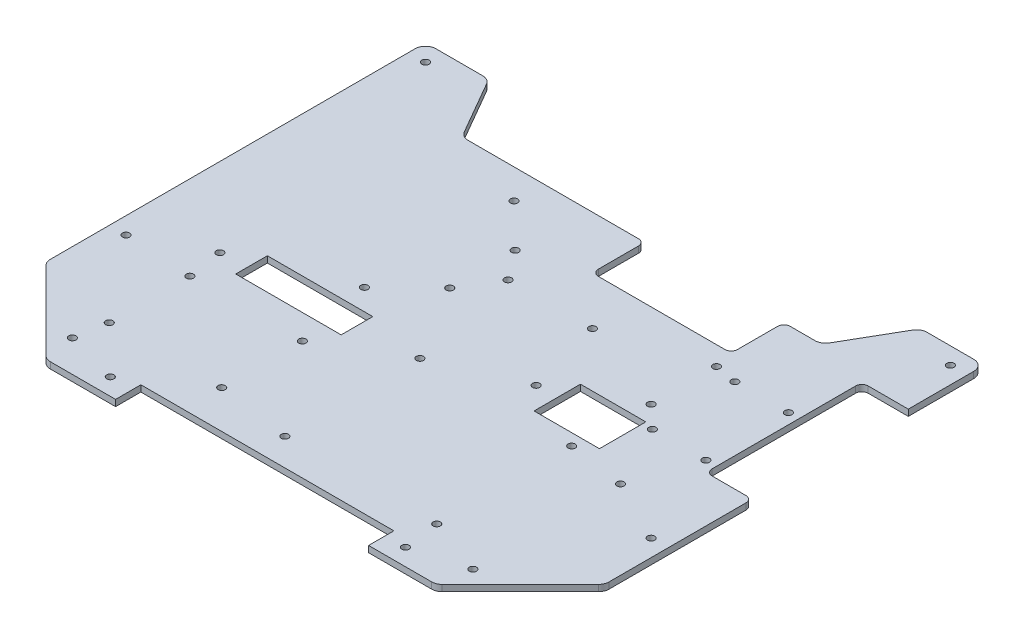
SolidWorks part; units mm, degrees
material "Acier non allié"
ref_plane "Front" through (0, 0, 0) normal (0, 0, 1) x (1, 0, 0)
ref_plane "Top" through (0, 0, 0) normal (0, 1, 0) x (1, 0, 0)
ref_plane "Right" through (0, 0, 0) normal (1, 0, 0) x (0, 0, -1)
sketch "Esquisse1" plane through (0, 0, 0) normal (0, 1, 0) x (1, 0, 0)
  line L0 (0, 0) -> (0, 190) construction
  line L1 (-92.5, 0) -> (92.5, 0)
  line L2 (92.5, 0) -> (132.5, 40)
  line L3 (132.5, 40) -> (132.5, 220)
  line L4 (132.5, 220) -> (102.5, 220)
  line L5 (102.5, 220) -> (85.1795, 190)
  line L6 (85.1795, 190) -> (-85.1795, 190)
  line L7 (-102.5, 220) -> (-85.1795, 190)
  line L8 (-132.5, 220) -> (-102.5, 220)
  line L9 (-132.5, 40) -> (-132.5, 220)
  line L10 (-92.5, 0) -> (-132.5, 40)
  dimension "D1" = 132.5
  dimension "D2" = 220
  dimension "D3" = 60
  dimension "D4" = 30
  dimension "D5" = 40
  dimension "D6" = 40
  dimension "D7" = 30
extrude "Boss.-Extru.1" add sketch "Esquisse1" along normal blind 3
fillet "Congé1" radius 5 10 edges at (92.5, 1.5, 0) (132.5, 1.5, -40) (132.5, 1.5, -220) (102.5, 1.5, -220) (85.1795, 1.5, -190) (-85.1795, 1.5, -190) (-102.5, 1.5, -220) (-132.5, 1.5, -220) (-92.5, 1.5, 0) (-132.5, 1.5, -40)
sketch "Esquisse2" plane through (0, 3, 0) normal (0, 1, 0) x (1, 0, 0)
  line L0 (0, 0) -> (0, 294.1173) construction
  line L2 (-90.4289, 0) -> (90.4289, 0) construction
  circle A0 centre (70, 8) radius 1
  circle A1 centre (124.5, 70) radius 1
  circle A2 centre (124.5, 212) radius 1
  circle A3 centre (-124.5, 212) radius 1
  circle A4 centre (-124.5, 70) radius 1
  circle A5 centre (-70, 8) radius 1
  dimension "D2" = 2
  dimension "D6" = 2
  dimension "D9" = 2
  dimension "D1" = 70
  dimension "D3" = 8
  dimension "D4" = 124.5
  dimension "D5" = 70
  dimension "D7" = 124.5
  dimension "D8" = 212
extrude "Enlèv. mat.-Extru.1" cut sketch "Esquisse2" against normal blind 3
hole_wizard "Dégagement M31" positions "Esquisse3" profile "Esquisse4" hole size "M3" standard "ISO" end condition through all
sketch "Esquisse3" plane through (0, 3, 0) normal (0, 1, 0) x (1, 0, 0)
  point P0 (70, 8)
  point P3 (-70, 8)
  point P6 (-124.5, 70)
  point P9 (-124.5, 212)
  point P12 (124.5, 212)
  point P15 (124.5, 70)
sketch "Esquisse4" plane through (70, 3, -8) normal (1, 0, 0) x (0, 0, 1)
  line L0 (0, 0) -> (0, 3)
  line L1 (0, 3) -> (1.7, 3)
  line L2 (1.7, 3) -> (1.7, 0)
  line L5 (1.7, 0) -> (0, 0)
  line L11 (0, -6.35) -> (0, 107.95) construction
  dimension "Diamètre du perçage jusqu'au prochain" = 3.4
  dimension "Profondeur du perçage jusqu'au prochain" = 3
sketch "Esquisse5" plane through (0, 3, 0) normal (0, 1, 0) x (1, 0, 0)
  line L0 (82.2927, 190) -> (-82.2927, 190) construction
  line L1 (67.5, 190) -> (1.5, 190)
  line L2 (67.5, 190) -> (67.5, 165)
  line L3 (67.5, 165) -> (1.5, 165)
  line L4 (1.5, 190) -> (1.5, 165)
  line L5 (132.5, 42.0711) -> (132.5, 215) construction
  line L6 (132.5, 184) -> (110.5, 184)
  line L7 (132.5, 184) -> (132.5, 110)
  line L8 (132.5, 110) -> (110.5, 110)
  line L9 (110.5, 184) -> (110.5, 110)
  line L10 (127.5, 220) -> (105.3868, 220) construction
  dimension "D1" = 25
  dimension "D2" = 65
  dimension "D3" = 131
  dimension "D4" = 36
  dimension "D5" = 110
  dimension "D6" = 22
extrude "Enlèv. mat.-Extru.2" cut sketch "Esquisse5" against normal through all
fillet "Congé2" radius 3 7 edges at (132.5, 1.5, -110) (110.5, 1.5, -110) (110.5, 1.5, -184) (67.5, 1.5, -190) (67.5, 1.5, -165) (1.5, 1.5, -165) (1.5, 1.5, -190)
sketch "Esquisse6" plane through (0, 3, 0) normal (0, 1, 0) x (1, 0, 0)
  line L0 (110.5, 140.5) -> (-167.6757, 140.5) construction
  line L1 (110.5, 181) -> (110.5, 113) construction
  line L2 (-90.4289, 0) -> (90.4289, 0) construction
  line L3 (110.5, 181) -> (110.5, 113) construction
  circle A0 centre (69.5, 156) radius 1
  circle A1 centre (-26, 156) radius 1
  circle A2 centre (-46.5, 176) radius 1
  circle A3 centre (69.5, 125) radius 1
  circle A4 centre (-26, 125) radius 1
  circle A5 centre (-46.5, 105) radius 1
  dimension "D4" = 2
  dimension "D6" = 2
  dimension "D10" = 2
  dimension "D1" = 140.5
  dimension "D2" = 41
  dimension "D3" = 15.5
  dimension "D5" = 136.5
  dimension "D7" = 15.5
  dimension "D8" = 35.5
  dimension "D9" = 157
extrude "Enlèv. mat.-Extru.3" cut sketch "Esquisse6" against normal through all
hole_wizard "Dégagement M32" positions "Esquisse7" profile "Esquisse8" hole size "M3" standard "ISO"
sketch "Esquisse7" plane through (0, 3, 0) normal (0, 1, 0) x (1, 0, 0)
  point P0 (-46.5, 105)
  point P3 (-26, 125)
  point P6 (-26, 156)
  point P9 (-46.5, 176)
  point P12 (69.5, 156)
  point P15 (69.5, 125)
sketch "Esquisse8" plane through (-46.5, 3, -105) normal (1, 0, 0) x (0, 0, 1)
  line L0 (0, 0) -> (0, 11.0215)
  line L1 (0, 11.0215) -> (1.7, 10)
  line L2 (1.7, 10) -> (1.7, 0)
  line L5 (1.7, 0) -> (0, 0)
  line L10 (0, 11.0215) -> (-1.7, 10) construction
  line L11 (0, -6.35) -> (0, 107.95) construction
  dimension "Diamètre du perçage" = 3.4
  dimension "Profondeur du perçage" = 10
  dimension "Angle de pointe" = 118
sketch "Esquisse9" plane through (0, 3, 0) normal (0, 1, 0) x (1, 0, 0)
  line L0 (132.5, 42.0711) -> (132.5, 107) construction
  line L1 (-90.4289, 0) -> (90.4289, 0) construction
  line L2 (-132.5, 215) -> (-132.5, 42.0711) construction
  line L3 (-39.16, 30) -> (-92.5, 30) construction
  line L4 (-39.16, 30) -> (-39.16, 68.24) construction
  line L5 (-39.16, 68.24) -> (-92.5, 68.24) construction
  line L6 (-92.5, 30) -> (-92.5, 68.24) construction
  line L7 (-4.16, 25) -> (-4.16, 89) construction
  line L8 (4.5, 165) -> (64.5, 165) construction
  line L9 (24.5, 142.1606) -> (-15.5, 142.1606) construction
  line L10 (110.5, 181) -> (110.5, 113) construction
  line L11 (113.5, 110) -> (129.5, 110) construction
  circle A0 centre (105.5, 115) radius 1
  circle A3 centre (105.5, 154.12) radius 1
  circle A6 centre (-92.5, 68.24) radius 1
  circle A7 centre (-39.16, 68.24) radius 1
  circle A8 centre (-39.16, 30) radius 1
  circle A9 centre (-92.5, 30) radius 1
  circle A10 centre (-4.16, 89) radius 1
  circle A11 centre (67.84, 89) radius 1
  circle A12 centre (-4.16, 25) radius 1
  circle A13 centre (67.84, 25) radius 1
  circle A14 centre (-15.5, 142.1606) radius 1
  circle A15 centre (24.5, 142.1606) radius 1
  circle A16 centre (34.5, 105.5) radius 1
  circle A17 centre (80.1, 115) radius 1
  circle A18 centre (80.1, 154.12) radius 1
  dimension "D2" = 2
  dimension "D4" = 2
  dimension "D17" = 2
  dimension "D18" = 2
  dimension "D19" = 2
  dimension "D20" = 2
  dimension "D21" = 2
  dimension "D22" = 2
  dimension "D23" = 2
  dimension "D24" = 2
  dimension "D32" = 2
  dimension "D33" = 2
  dimension "D34" = 2
  dimension "D11" = 2
  dimension "D12" = 2
  dimension "D5" = 27
  dimension "25" = 27
  dimension "D10" = 39.12
  dimension "D13" = 38.24
  dimension "D14" = 53.34
  dimension "D15" = 30
  dimension "D16" = 40
  dimension "D25" = 72
  dimension "D26" = 72
  dimension "D27" = 64
  dimension "D28" = 64
  dimension "D29" = 35
  dimension "D30" = 25
  dimension "D31" = 25
  dimension "D36" = 38
  dimension "D37" = 40
  dimension "D39" = 10
  dimension "D7" = 5
  dimension "D8" = 25.4
  dimension "D9" = 25.4
  dimension "D40" = 39.12
  dimension "D35" = 59.5
  dimension "D38" = 76
extrude "Enlèv. mat.-Extru.4" cut sketch "Esquisse9" against normal through all
hole_wizard "Dégagement M33" positions "Esquisse10" profile "Esquisse11" hole size "M3" standard "ISO"
sketch "Esquisse10" plane through (0, 3, 0) normal (0, 1, 0) x (1, 0, 0)
  point P3 (105.5, 115)
  point P9 (105.5, 154.12)
  point P14 (80.1, 154.12)
  point P17 (80.1, 115)
sketch "Esquisse11" plane through (105.5, 3, -115) normal (1, 0, 0) x (0, 0, 1)
  line L0 (0, 0) -> (0, 11.0215)
  line L1 (0, 11.0215) -> (1.7, 10)
  line L2 (1.7, 10) -> (1.7, 0)
  line L5 (1.7, 0) -> (0, 0)
  line L10 (0, 11.0215) -> (-1.7, 10) construction
  line L11 (0, -6.35) -> (0, 107.95) construction
  dimension "Diamètre du perçage" = 3.4
  dimension "Profondeur du perçage" = 10
  dimension "Angle de pointe" = 118
sketch "Esquisse12" plane through (0, 3, 0) normal (0, 1, 0) x (1, 0, 0)
  line L2 (-90.4289, 0) -> (90.4289, 0) construction
  line L3 (95, 15) -> (-95, 15) construction
  line L4 (95, 15) -> (95, 85) construction
  line L5 (95, 85) -> (-95, 85) construction
  line L6 (-95, 15) -> (-95, 85) construction
  line L7 (132.5, 42.0711) -> (132.5, 107) construction
  circle A4 centre (-95, 85) radius 1
  circle A5 centre (95, 85) radius 1
  circle A6 centre (95, 15) radius 1
  circle A7 centre (-95, 15) radius 1
  point P6 (95, 50)
  dimension "D5" = 2
  dimension "D6" = 2
  dimension "D7" = 2
  dimension "D8" = 2
  dimension "D1" = 70
  dimension "D2" = 190
  dimension "D3" = 15
  dimension "D4" = 37.5
extrude "Enlèv. mat.-Extru.5" cut sketch "Esquisse12" against normal through all and the other way through all
hole_wizard "Dégagement M34" positions "Esquisse13" profile "Esquisse14" hole size "M3" standard "ISO"
sketch "Esquisse13" plane through (0, 3, 0) normal (0, 1, 0) x (1, 0, 0)
  point P3 (-92.5, 68.24)
  point P6 (-92.5, 30)
  point P9 (-39.16, 30)
  point P12 (-39.16, 68.24)
  point P16 (-4.16, 25)
  point P19 (67.84, 25)
  point P22 (-4.16, 89)
  point P25 (67.84, 89)
  point P29 (34.5, 105.5)
  point P32 (24.5, 142.1606)
  point P35 (-15.5, 142.1606)
sketch "Esquisse14" plane through (-92.5, 3, -68.24) normal (1, 0, 0) x (0, 0, 1)
  line L0 (0, 0) -> (0, 11.0215)
  line L1 (0, 11.0215) -> (1.7, 10)
  line L2 (1.7, 10) -> (1.7, 0)
  line L5 (1.7, 0) -> (0, 0)
  line L10 (0, 11.0215) -> (-1.7, 10) construction
  line L11 (0, -6.35) -> (0, 107.95) construction
  dimension "Diamètre du perçage" = 3.4
  dimension "Profondeur du perçage" = 10
  dimension "Angle de pointe" = 118
hole_wizard "Dégagement M35" positions "Esquisse15" profile "Esquisse16" hole size "M3" standard "ISO"
sketch "Esquisse15" plane through (0, 3, 0) normal (0, 1, 0) x (1, 0, 0)
  point P0 (-95, 15)
  point P3 (-95, 85)
  point P6 (95, 85)
  point P9 (95, 15)
sketch "Esquisse16" plane through (-95, 3, -15) normal (1, 0, 0) x (0, 0, 1)
  line L0 (0, 0) -> (0, 11.0215)
  line L1 (0, 11.0215) -> (1.7, 10)
  line L2 (1.7, 10) -> (1.7, 0)
  line L5 (1.7, 0) -> (0, 0)
  line L10 (0, 11.0215) -> (-1.7, 10) construction
  line L11 (0, -6.35) -> (0, 107.95) construction
  dimension "Diamètre du perçage" = 3.4
  dimension "Profondeur du perçage" = 10
  dimension "Angle de pointe" = 118
sketch "Esquisse17" plane through (0, 3, 0) normal (0, 1, 0) x (1, 0, 0)
  line L0 (-90.4289, 0) -> (90.4289, 0) construction
  line L1 (-82.5, 95) -> (-32.5, 95)
  line L2 (-82.5, 95) -> (-82.5, 80)
  line L3 (-82.5, 80) -> (-32.5, 80)
  line L4 (-32.5, 95) -> (-32.5, 80)
  line L5 (-132.5, 215) -> (-132.5, 42.0711) construction
  line L6 (132.5, 42.0711) -> (132.5, 107) construction
  line L7 (44.5, 116.5) -> (75.5, 116.5)
  line L8 (44.5, 116.5) -> (44.5, 94.5)
  line L9 (44.5, 94.5) -> (75.5, 94.5)
  line L10 (75.5, 116.5) -> (75.5, 94.5)
  line L11 (82.2927, 190) -> (70.5, 190) construction
  line L13 (-59.5, 12) -> (60.5, 12)
  line L14 (-59.5, 12) -> (-59.5, 0)
  line L15 (-59.5, 0) -> (60.5, 0)
  line L16 (60.5, 12) -> (60.5, 0)
  point P20 (60.5, 0)
  dimension "D1" = 50
  dimension "D2" = 15
  dimension "D3" = 80
  dimension "D4" = 50
  dimension "D5" = 31
  dimension "D6" = 22
  dimension "D7" = 57
  dimension "D8" = 73.5
  dimension "D9" = 12
  dimension "D11" = 120
  dimension "D12" = 72
extrude "Enlèv. mat.-Extru.6" cut sketch "Esquisse17" against normal up to surface (3 mm away) up to face at (-95, 0, -13.3)
equation "\"WIDTH\"= 300mm'Total width of the robot"
equation "\"LENGTH\"= 220mm'Total length of the robot"
equation "\"CUT_DEPTH\"= 45mm'Depth of the cut on the edges of the plate"
equation "\"Plate_th\"= 3mm'Thickness of the plate"
equation "\"D1\"= \"Plate_th\""
equation "\"D5@Esquisse9\"=\"25@Esquisse9\""
